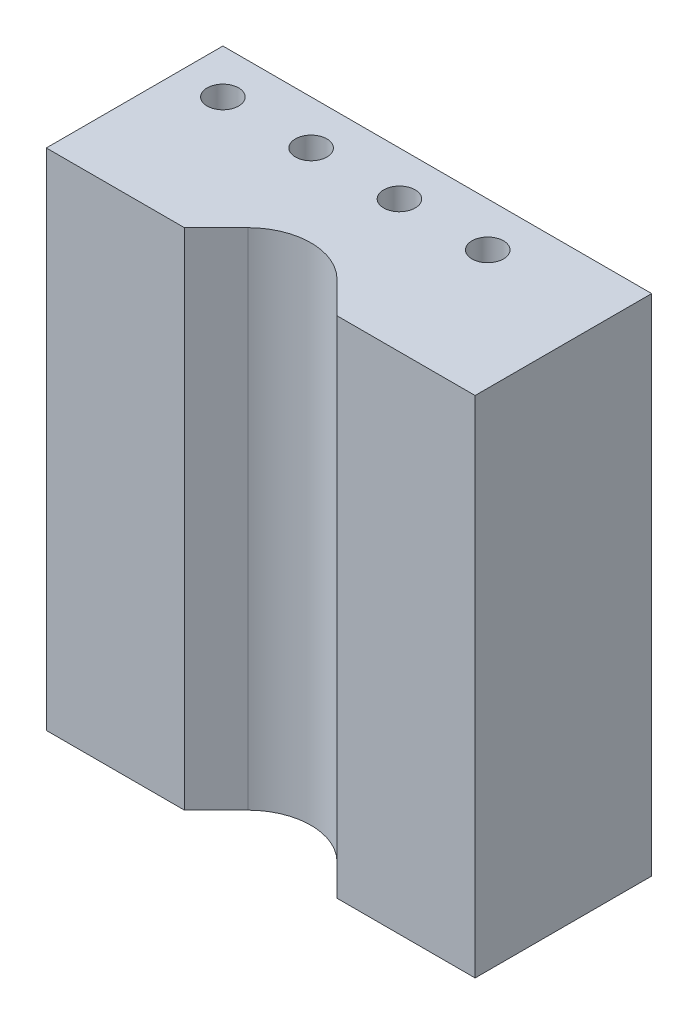
SolidWorks part; units mm, degrees
ref_plane "前视基准面" through (0, 0, 0) normal (0, 0, 1) x (1, 0, 0)
ref_plane "上视基准面" through (0, 0, 0) normal (0, 1, 0) x (1, 0, 0)
ref_plane "右视基准面" through (0, 0, 0) normal (1, 0, 0) x (0, 0, -1)
other "Configuration Table"
sketch "草图1" plane through (0, 0, 0) normal (0, 1, 0) x (1, 0, 0)
  line L0 (28.8848, 10.546) -> (-13.9053, 10.546) construction
  line L1 (-13.9053, 10.546) -> (-3.9053, -4.454) construction
  line L2 (-3.9053, -4.454) -> (28.8848, -4.454) construction
  line L7 (28.8848, -4.454) -> (28.8848, 10.546) construction
  line L8 (-3.5, 3.5) -> (-3.5, -10.5)
  line L9 (-3.5, -10.5) -> (1.4497, -10.5)
  line L10 (1.4497, -10.5) -> (7.4957, -4.454) construction
  line L11 (7.4957, -4.454) -> (13.5043, -4.454) construction
  line L12 (13.5043, -4.454) -> (19.5503, -10.5)
  line L13 (19.5503, -10.5) -> (24.5, -10.5)
  line L14 (24.5, -10.5) -> (24.5, 3.5) construction
  line L15 (24.5, 3.5) -> (-3.5, 3.5)
  line L16 (24.5, 3.5) -> (30.5, 3.5)
  line L17 (30.5, 3.5) -> (30.5, -10.5)
  line L18 (30.5, -10.5) -> (24.5, -10.5)
  line L19 (1.4497, -10.5) -> (7.4497, -10.5)
  line L20 (7.4497, -10.5) -> (13.4957, -4.454)
  line L21 (13.4957, -4.454) -> (13.5043, -4.454)
  circle A0 centre (0, 0) radius 1.25
  circle A1 centre (7, 0) radius 1.25
  circle A2 centre (14, 0) radius 1.25
  circle A3 centre (21, 0) radius 1.25
  circle A4 centre (7, -7) radius 1.25 [skipped]
  circle A5 centre (14, -7) radius 1.25 [skipped]
  circle A6 centre (21, -7) radius 1.25
  circle A7 centre (0, -7) radius 1.25
  point P25 (0, 0)
  dimension "D1" = 2.5
  dimension "D2" = 4
  dimension "D4" = 4.454
  dimension "D5" = 3.5
  dimension "D6" = 3.5
  dimension "D7" = 3.5
  dimension "D8" = 3.5
  dimension "D9" = 135
  dimension "D10" = 3.5
  dimension "D11" = 3.5
  dimension "D12" = 7
  dimension "D13" = 7
  dimension "D14" = 6
  dimension "D15" = 6
  dimension "D3" = 2
extrude "凸台-拉伸1" add sketch "草图1" along normal blind 40
sketch "草图2" plane through (0, 0, 0) normal (0, -1, 0) x (1, 0, 0)
  circle A0 centre (21, 7) radius 1.25 construction
  circle A1 centre (21, 0) radius 1.25 construction
  circle A2 centre (14, 0) radius 1.25 construction
  circle A3 centre (7, 0) radius 1.25 construction
  circle A4 centre (0, 0) radius 1.25 construction
  circle A5 centre (0, 7) radius 1.25 construction
  circle A6 centre (21, 7) radius 1.25
  circle A7 centre (21, 0) radius 1.25
  circle A8 centre (14, 0) radius 1.25
  circle A9 centre (7, 0) radius 1.25
  circle A10 centre (0, 0) radius 1.25
  circle A11 centre (0, 7) radius 1.25
  circle A12 centre (27, 7) radius 1.25
  circle A13 centre (27, 0) radius 1.25
  circle A14 centre (20, 0) radius 1.25
  circle A15 centre (13, 0) radius 1.25
  circle A16 centre (6, 0) radius 1.25
  circle A17 centre (6, 7) radius 1.25
  circle M10 centre (0, 0) radius 1.25
  circle M11 centre (7, 0) radius 1.25
  circle M12 centre (14, 0) radius 1.25
  circle M13 centre (21, 0) radius 1.25
  circle M14 centre (21, 7) radius 1.25
  circle M15 centre (0, 7) radius 1.25
  dimension "D1" = 2
extrude "凸台-拉伸2" add sketch "草图2" against normal blind 30 contours M15 | M10 | A16 M11 | A16 A9 | A15 M12 | A15 A8 | A14 M13 | A14 A7 | M14 region at (21, 0, 7) region at (21.5093, 0, 0) region at (20.5, 0, 0) region at (14.5093, 0, 0) region at (13.5, 0, 0) region at (7.5093, 0, 0) region at (6.5, 0, 0) region at (0, 0, 0) region at (0, 0, 7)
extrude "切除-拉伸1" cut sketch "草图2<3>" against normal blind 10 contours A17 | A16 M11 | A16 M11 | A15 M12 | A15 M12 | A14 M13 | A14 M13 | A13 | A12 region at (20.5, 0, 0) region at (19.4907, 0, 0) region at (13.5, 0, 0) region at (12.4907, 0, 0) region at (6.5, 0, 0) region at (5.4907, 0, 0) region at (27, 0, 7) region at (27, 0, 0) region at (6, 0, 7)
sketch "草图2<3>" plane through (0, 0, 0) normal (0, -1, 0) x (1, 0, 0) same geometry as "草图2"
sketch "草图3" plane through (0, 40, 0) normal (0, 1, 0) x (1, 0, 0)
  line L0 (28.9728, 10.546) -> (-13.8174, 10.546)
  line L1 (-13.8174, 10.546) -> (-3.8174, -4.454)
  line L2 (-3.8174, -4.454) -> (28.9728, -4.454)
  line L3 (28.9728, -4.454) -> (28.9728, 10.546)
  line L4 (7.4497, -10.5) -> (13.4957, -4.454) construction
  line L5 (7.4497, -10.5) -> (13.4957, -4.454)
  line L6 (1.4497, -10.5) -> (7.4957, -4.454)
  line L7 (-3.5, -10.5) -> (7.4497, -10.5) construction
  line L8 (24.5, 3.5) -> (24.5, -10.5)
  line L9 (30.5, 3.5) -> (-3.5, 3.5) construction
  line L10 (19.5503, -10.5) -> (30.5, -10.5) construction
  line L11 (30.5, -10.5) -> (30.5, 3.5) construction
  line L12 (30.5, 3.5) -> (-3.5, 3.5)
  line L13 (30.5, 3.5) -> (30.9728, 3.5)
  line L14 (30.9728, 3.5) -> (30.9728, -6.454)
  line L15 (30.9728, -6.454) -> (-3.5, -6.454)
  line L16 (-3.5, 3.5) -> (-3.5, -10.5) construction
  line L17 (-3.5, -6.454) -> (-3.5, -4.454)
  circle A2 centre (21, -7) radius 1.25 construction
  circle A3 centre (0, -7) radius 1.25 construction
  circle A4 centre (21, -7) radius 1.25
  circle A5 centre (0, -7) radius 1.25
  circle M7 centre (21, -7) radius 1.25
  circle M20 centre (0, -7) radius 1.25
  dimension "D1" = 6
  dimension "D2" = 6
  dimension "D3" = 2
  dimension "D4" = 2
extrude "凸台-拉伸3" add sketch "草图3" against normal up to surface (10 mm away) contours L15 M20 | L15 M7 | L15 M7 | L15 M20 region at (0, 40, 6.1643) region at (0, 40, 7.2511) region at (21, 40, 7.2511) region at (21, 40, 6.1643) up to face at (0, 30, 5.75)
sketch "草图4" plane through (0, 40, 0) normal (0, 1, 0) x (1, 0, 0)
  circle A0 centre (21, 0) radius 1.25 construction
  circle A1 centre (14, 0) radius 1.25 construction
  circle A2 centre (7, 0) radius 1.25 construction
  circle A3 centre (0, 0) radius 1.25 construction
  circle A4 centre (21, 0) radius 1.25
  circle A5 centre (14, 0) radius 1.25
  circle A6 centre (7, 0) radius 1.25
  circle A7 centre (0, 0) radius 1.25
extrude "切除-拉伸2" cut sketch "草图4" against normal blind 15
sketch "草图5" plane through (0, 0, 0) normal (0, -1, 0) x (1, 0, 0)
  circle A0 centre (6, 7) radius 1.25 construction
  circle A1 centre (27, 7) radius 1.25 construction
  circle A2 centre (27, 0) radius 1.25 construction
  circle A3 centre (20, 0) radius 1.25 construction
  circle A4 centre (13, 0) radius 1.25 construction
  circle A5 centre (6, 0) radius 1.25 construction
  circle A6 centre (6, 7) radius 1.25
  circle A7 centre (27, 7) radius 1.25
  circle A8 centre (27, 0) radius 1.25
  circle A9 centre (20, 0) radius 1.25
  circle A10 centre (13, 0) radius 1.25
  circle A11 centre (6, 0) radius 1.25
extrude "切除-拉伸3" cut sketch "草图5" against normal blind 15
sketch "草图6" plane through (0, 40, 0) normal (0, 1, 0) x (1, 0, 0)
  line L0 (13.4957, -4.454) -> (13.5043, -4.454) construction
  line L1 (13.5043, -4.454) -> (19.5503, -10.5) construction
  line L2 (7.4497, -10.5) -> (13.4957, -4.454) construction
  line L3 (13.4957, -4.454) -> (13.5043, -4.454)
  line L4 (13.5043, -4.454) -> (19.5503, -10.5)
  line L5 (7.4497, -10.5) -> (13.4957, -4.454)
  arc A0 (9.9645, -7.9853) -> (17.0355, -7.9853) centre (13.5, -11.5208) cw
  point P7 (0, 0)
  line M9 (13.4957, -4.454) -> (13.5043, -4.454)
  line M10 (13.5043, -4.454) -> (19.5503, -10.5)
  dimension "D1" = 5
extrude "凸台-拉伸4" add sketch "草图6" against normal up to surface (40 mm away) contours L5 A0 M10 M9 region at (13.5, 40, 6.0292) up to face at (27, 0, 5.75)
